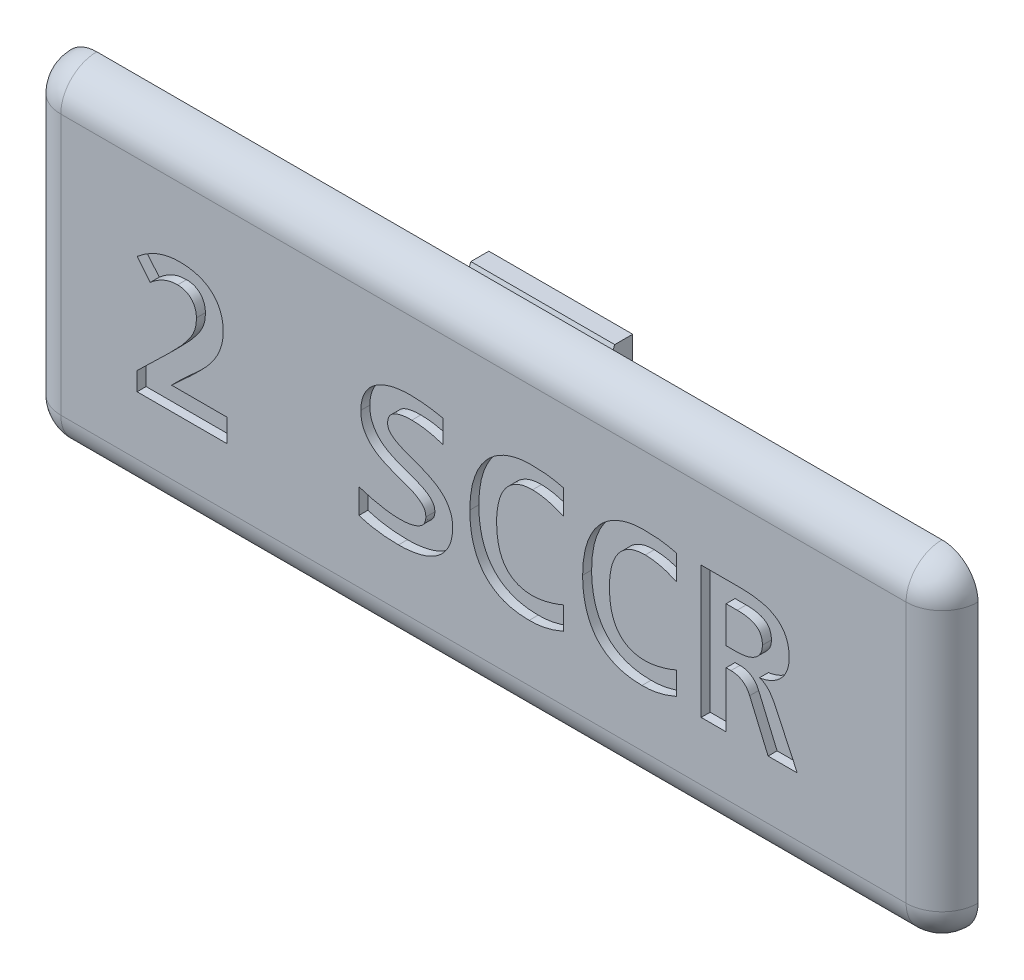
SolidWorks part; units mm, degrees
ref_plane "Front Plane" through (0, 0, 0) normal (0, 0, 1) x (1, 0, 0)
ref_plane "Top Plane" through (0, 0, 0) normal (0, 1, 0) x (1, 0, 0)
ref_plane "Right Plane" through (0, 0, 0) normal (1, 0, 0) x (0, 0, -1)
sketch "Sketch1" plane through (0, 0, 0) normal (0, 0, 1) x (1, 0, 0)
  line L13 (25.5, -7.25) -> (25.5, 7.25) construction
  line L14 (-23.5, -9.25) -> (-5, -9.25) construction
  line L15 (-25.5, 7.25) -> (-25.5, -7.25) construction
  line L16 (13, 9.25) -> (-23.5, 9.25) construction
  line L17 (25.5, -7.25) -> (25.5, 7.25)
  line L18 (-23.5, -9.25) -> (23.5, -9.25)
  line L19 (-25.5, 7.25) -> (-25.5, -7.25)
  line L20 (23.5, 9.25) -> (-23.5, 9.25)
  line L28 (23.75, -7.75) -> (23.75, 7.75)
  line L29 (-23.75, -7.5) -> (11.5, -7.5)
  line L30 (-23.75, 7.5) -> (-23.75, -7.5)
  line L31 (13, 7.5) -> (-23.75, 7.5)
  line L32 (-23.75, -7.5) -> (23.75, -7.5) construction
  line L33 (-23.75, 7.5) -> (-23.75, -7.5) construction
  line L34 (23.75, 7.5) -> (-23.75, 7.5) construction
  line L35 (23.75, -7.75) -> (23.75, 7.75) construction
  arc A0 (25.5, 7.25) -> (23.5, 9.25) centre (23.5, 7.25) ccw construction
  arc A1 (23.5, -9.25) -> (25.5, -7.25) centre (23.5, -7.25) ccw construction
  arc A2 (-25.5, -7.25) -> (-23.5, -9.25) centre (-23.5, -7.25) ccw construction
  arc A3 (-23.5, 9.25) -> (-25.5, 7.25) centre (-23.5, 7.25) ccw construction
  arc A4 (25.5, 7.25) -> (23.5, 9.25) centre (23.5, 7.25) ccw
  arc A5 (23.5, -9.25) -> (25.5, -7.25) centre (23.5, -7.25) ccw
  arc A6 (-25.5, -7.25) -> (-23.5, -9.25) centre (-23.5, -7.25) ccw
  arc A7 (-23.5, 9.25) -> (-25.5, 7.25) centre (-23.5, 7.25) ccw
  dimension "D1" = 0.25
  dimension "D2" = 0.25
extrude "Boss-Extrude1" add sketch "Sketch1" along normal blind 2
sketch "Sketch3" plane through (0, 0, 0) normal (0, 0, -1) x (-1, 0, 0)
  line L0 (-23.75, -7.75) -> (-23.75, 7.75) construction
  line L1 (-23.75, 7.5) -> (23.75, 7.5) construction
  line L2 (23.75, 7.5) -> (23.75, -7.5) construction
  line L3 (23.75, -7.5) -> (-23.75, -7.5) construction
  line L4 (-23.75, -7.5) -> (-23.75, 7.5)
  line L5 (-23.75, 7.5) -> (23.75, 7.5)
  line L6 (23.75, 7.5) -> (23.75, -7.5)
  line L7 (23.75, -7.5) -> (-23.75, -7.5)
extrude "Boss-Extrude2" add sketch "Sketch3" along normal blind 1
sketch "Sketch4" plane through (0, 0, -1) normal (0, 0, -1) x (-1, 0, 0)
  line L0 (-23.75, -7.5) -> (23.75, -7.5) construction
  line L1 (-8.75, -7.5) -> (-18.25, -7.5)
  line L2 (-8.75, -7.5) -> (-8.75, -2.5)
  line L3 (-8.75, -2.5) -> (-18.25, -2.5)
  line L4 (-18.25, -7.5) -> (-18.25, -2.5)
  line L5 (-11.5, -7.75) -> (-15.5, -7.75) construction
  point P4 (-13.5, -2.5)
  point P9 (-13.5, -7.75)
  dimension "D1" = 5
  dimension "D3" = 9.5
extrude "Cut-Extrude1" cut sketch "Sketch4" against normal blind 1
sketch "Sketch5" plane through (0, 0, -1) normal (0, 0, -1) x (-1, 0, 0)
  line L1 (-13, 7.75) -> (-21, 7.75)
  line L2 (-13, 7.75) -> (-13, -0.75)
  line L3 (-13, -0.75) -> (-21, -0.75)
  line L4 (-21, 7.75) -> (-21, -0.75)
  line L5 (-24, 7.75) -> (24, 7.75) construction
  dimension "D1" = 8
  dimension "D2" = 8.5
extrude "Cut-Extrude2" cut sketch "Sketch5" against normal blind 1
sketch "Sketch6" plane through (0, 0, 0) normal (0, 0, -1) x (-1, 0, 0)
  line L1 (-11.5, -9.25) -> (-15.5, -9.25)
  line L2 (-11.5, -9.25) -> (-11.5, -7.5)
  line L3 (-11.5, -7.5) -> (-15.5, -7.5)
  line L4 (-15.5, -9.25) -> (-15.5, -7.5)
  line L6 (23.75, -7.5) -> (-23.75, -7.5) construction
  line L8 (-11.5, -9.25) -> (-15.5, -9.25) construction
  line L9 (23.5, -9.25) -> (-23.5, -9.25) construction
  point P8 (-13.5, -7.5)
  point P11 (-13.5, -9.25)
  dimension "D1" = 4
extrude "Boss-Extrude3" add sketch "Sketch6" along normal blind 1.75
sketch "Sketch8" plane through (0, 0, 0) normal (1, 0, 0) x (0, 0, -1)
  line L1 (1, -7.5) -> (1, 7.5) construction
  line L2 (2.3, 6.05) -> (2.3, 8.25)
  line L3 (1, 5.25) -> (1, 7.5)
  line L4 (1, 7.5) -> (1.3, 8.25)
  line L5 (1.3, 8.25) -> (2.3, 8.25)
  line L6 (2.3, 6.05) -> (1, 5.25)
  dimension "D1" = 0.3
  dimension "D2" = 1
  dimension "D3" = 3
  dimension "D4" = 0.75
  dimension "D5" = 0.8
extrude "Boss-Extrude4" add sketch "Sketch8" against normal blind 4 and the other way blind 4
mirror "Mirror1" about plane through (0, 0, 0) normal (0, 1, 0) of "Boss-Extrude4"
fillet "Fillet1" radius 2 8 edges at (-24.9142, 8.6642, 2) (0, 9.25, 2) (24.9142, 8.6642, 2) (25.5, 0, 2) (24.9142, -8.6642, 2) (0, -9.25, 2) (-24.9142, -8.6642, 2) (-25.5, 0, 2)
sketch "Sketch9" plane through (0, 0, 2) normal (0, 0, 1) x (1, 0, 0)
  line L0 (-20, -4) -> (20, -4) construction
  line L1 (-23.75, -7.5) -> (23.75, -7.5) construction
  text T0 "<b>2 SCCR</b>" font "Consolas" height in points 28
  point P2 (0, -4)
  dimension "D1" = 40
  dimension "D2" = 3.5
extrude "Cut-Extrude3" cut sketch "Sketch9" against normal blind 0.5
